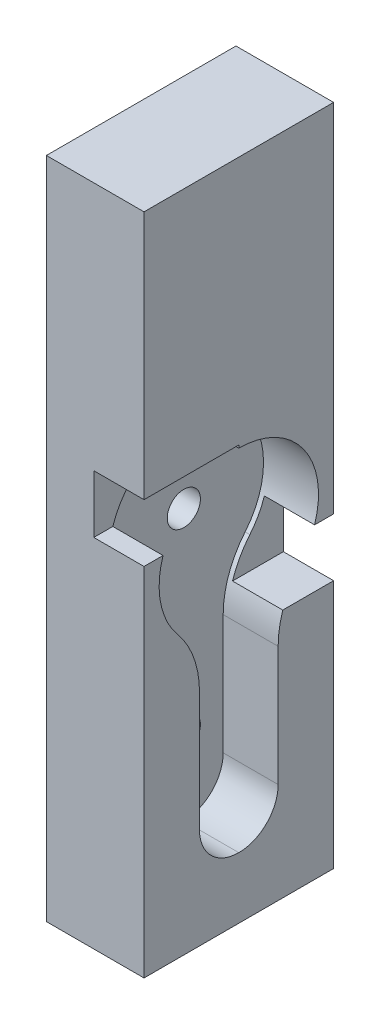
SolidWorks part; units mm, degrees
material "ABS"
ref_plane "Front Plane" through (0, 0, 0) normal (0, 0, 1) x (1, 0, 0)
ref_plane "Top Plane" through (0, 0, 0) normal (0, 1, 0) x (1, 0, 0)
ref_plane "Right Plane" through (0, 0, 0) normal (1, 0, 0) x (0, 0, -1)
sketch "Sketch1" plane through (0, 0, 0) normal (1, 0, 0) x (0, 0, -1)
  line L1 (-10, 10) -> (10, 10)
  line L2 (-10, 10) -> (-10, -10)
  line L3 (-10, -10) -> (10, -10)
  line L4 (10, 10) -> (10, -10)
  line L5 (-10, 10) -> (10, -10) construction
  line L6 (-10, -10) -> (10, 10) construction
  point P0 (0, 0)
  dimension "D1" = 20
  dimension "D2" = 20
extrude "Boss-Extrude1" add sketch "Sketch1" along normal blind 20
sketch "Sketch2" plane through (20, 0, 0) normal (1, 0, 0) x (0, 0, -1)
  line L1 (-10, 35) -> (10, 35)
  line L2 (-10, 35) -> (-10, -35)
  line L3 (-10, -35) -> (10, -35)
  line L4 (10, 35) -> (10, -35)
  line L5 (-10, 35) -> (10, -35) construction
  line L6 (-10, -35) -> (10, 35) construction
  point P0 (0, 0)
  dimension "D1" = 20
  dimension "D2" = 70
extrude "Boss-Extrude2" add sketch "Sketch2" along normal blind 10.3
sketch "Sketch4" plane through (30.3, 0, 0) normal (1, 0, 0) x (0, 0, -1)
  line L0 (0, 7.65) -> (0, 8.1702) construction
  line L1 (7.65, 7.65) -> (-7.65, 7.65) construction
  line L17 (4.15, -26.55) -> (-4.15, -26.55) construction
  line L18 (-7.65, 7.65) -> (7.65, 7.65) construction
  line L22 (-7.65, 7.65) -> (-7.65, -27.55) construction
  line L23 (-7.65, -27.55) -> (7.65, -27.55) construction
  line L24 (7.65, 7.65) -> (7.65, -27.55) construction
  line L25 (-7.65, 7.65) -> (7.65, -27.55) construction
  line L26 (-7.65, -27.55) -> (7.65, 7.65) construction
  line L27 (4.15, -26.55) -> (4.15, -28.55) construction
  line L28 (4.15, -28.55) -> (-4.15, -28.55) construction
  line L29 (-4.15, -26.55) -> (-4.15, -28.55) construction
  line L30 (4.15, -26.55) -> (-4.15, -28.55) construction
  line L31 (4.15, -28.55) -> (-4.15, -26.55) construction
  line L34 (4.15, -28.55) -> (-4.15, -28.55)
  line L35 (-4.15, -28.55) -> (-4.15, -7.3118)
  line L36 (4.15, -28.55) -> (4.15, -7.3118)
  arc A1 (4.15, -6.4265) -> (-4.15, -6.4265) centre (0, 0) ccw construction
  arc A2 (4.15, -7.3118) -> (-4.15, -7.3118) centre (0, 0) ccw
  point P1 (0, -27.55)
  point P7 (0, -13.75)
  point P10 (0, 7.65)
  point P14 (0, -9.95)
  dimension "D1" = 15.3
  dimension "D5" = 2
  dimension "D2" = 15.3
  dimension "D3" = 35.2
  dimension "D4" = 8.3
extrude "Cut-Extrude1" cut sketch "Sketch4" against normal blind 5.8
fillet "Fillet1" radius 4.15 2 edges at (27.4, -28.55, 4.15) (27.4, -28.55, -4.15)
fillet "Fillet2" radius 10 2 edges at (27.4, -7.3118, 4.15) (27.4, -7.3118, -4.15)
sketch "Sketch5" plane through (0, 0, 0) normal (-1, 0, 0) x (0, 0, 1)
  circle A0 centre (0, 0) radius 1.75
  dimension "D1" = 3.5
extrude "Cut-Extrude2" cut sketch "Sketch5" against normal through all
sketch "Sketch6" plane through (24.5, 0, 0) normal (1, 0, 0) x (0, 0, -1)
  line L0 (0, -19.35) -> (0, 0) construction
  line L1 (0, -25.65) -> (0, -23.15) construction
  line L2 (0, -23.15) -> (0, -21.85) construction
  line L3 (0, -21.85) -> (0, -19.35) construction
  line L5 (0, 0) -> (1.164, 0) construction
  line L6 (0, 0) -> (0, -9.35) construction
  line L7 (0, -9.35) -> (1.164, -9.35) construction
  line L8 (1.164, 0) -> (1.164, -9.35) construction
  line L9 (0, 0) -> (1.164, -9.35) construction
  line L10 (0, -9.35) -> (1.164, 0) construction
  circle A0 centre (0, -20.6) radius 1.75
  circle A1 centre (0, -9.35) radius 1.75 construction
  point P11 (0.582, -4.675)
  dimension "D5" = 3.5
  dimension "D6" = 9.35
  dimension "D7" = 3.5
  dimension "D1" = 19.35
  dimension "D2" = 2.5
  dimension "D3" = 1.3
  dimension "D4" = 2.5
extrude "Cut-Extrude3" cut sketch "Sketch6" against normal up to next
sketch "Sketch13" plane through (0, 0, 0) normal (-1, 0, 0) x (0, 0, 1)
  line L1 (-10, 10) -> (10, 10)
  line L2 (-10, 10) -> (-10, -10)
  line L3 (-10, -10) -> (10, -10)
  line L4 (10, 10) -> (10, -10)
extrude "Cut-Extrude9" cut sketch "Sketch13" against normal up to surface (20 mm away) up to face at (20, 22.5, 0)
sketch "Sketch29" plane through (30.3, 0, 0) normal (1, 0, 0) x (0, 0, -1)
  line L0 (0, 0) -> (0, 2.6) construction
  line L1 (15.1094, -8.7) -> (15.1094, -2.6)
  line L2 (0, 2.6) -> (-15.1094, 2.6)
  line L4 (0, 2.6) -> (0, 3.8)
  line L5 (0, 3.8) -> (0, 7.5)
  line L6 (0, 7.5) -> (0, 8.7)
  line L7 (0, 8.7) -> (-15.1094, 8.7)
  line L8 (-15.1094, 8.7) -> (-15.1094, 2.6)
  line L9 (0, -2.6) -> (15.1094, -2.6)
  line L10 (0, -2.6) -> (0, -3.8)
  line L11 (0, -3.8) -> (0, -7.5)
  line L12 (0, -7.5) -> (0, -8.7)
  line L13 (0, -8.7) -> (15.1094, -8.7)
  point P19 (0, 0)
  dimension "D1" = 2.6
  dimension "D2" = 1.2
  dimension "D3" = 3.7
  dimension "D4" = 1.2
  dimension "D5" = 2
extrude "Cut-Extrude18" cut sketch "Sketch29" against normal blind 5.3
